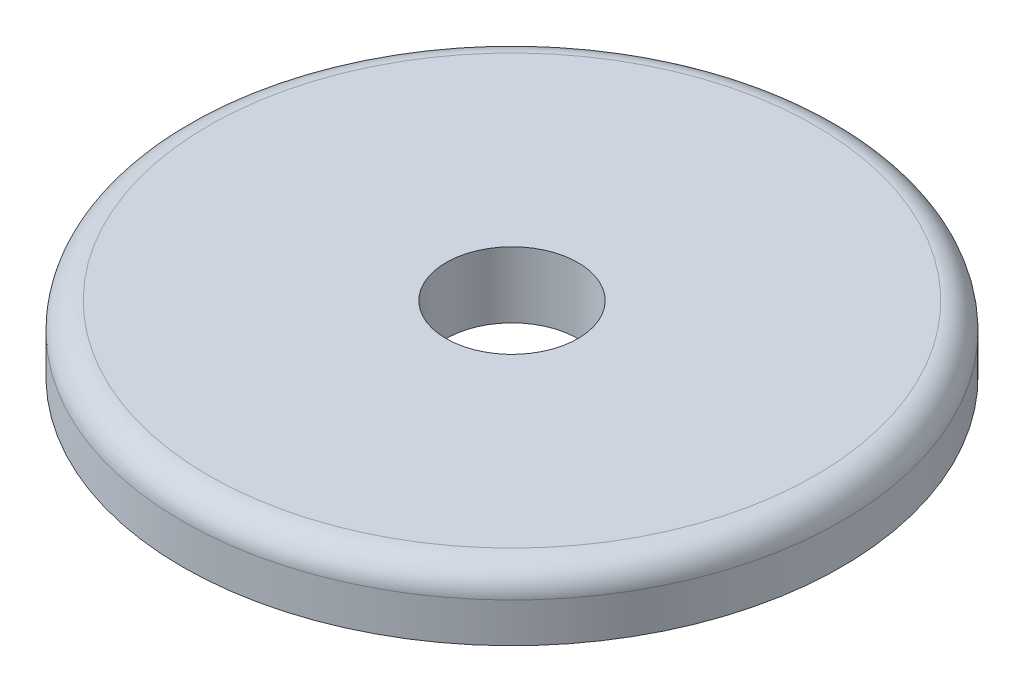
SolidWorks part; units mm, degrees
ref_plane "Front" through (0, 0, 0) normal (0, 0, 1) x (1, 0, 0)
ref_plane "Top" through (0, 0, 0) normal (0, 1, 0) x (1, 0, 0)
ref_plane "Right" through (0, 0, 0) normal (1, 0, 0) x (0, 0, -1)
sketch "Sketch2" plane through (0, 0, 0) normal (0, 1, 0) x (1, 0, 0)
  circle A0 centre (0, 0) radius 63.5
  circle A1 centre (0, 0) radius 12.7
  dimension "D1" = 25.4
  dimension "D2" = 127
extrude "Boss-Extrude1" add sketch "Sketch2" along normal blind 12.7
fillet "Fillet1" radius 5.08 1 edges at (0, 12.7, 63.5)
